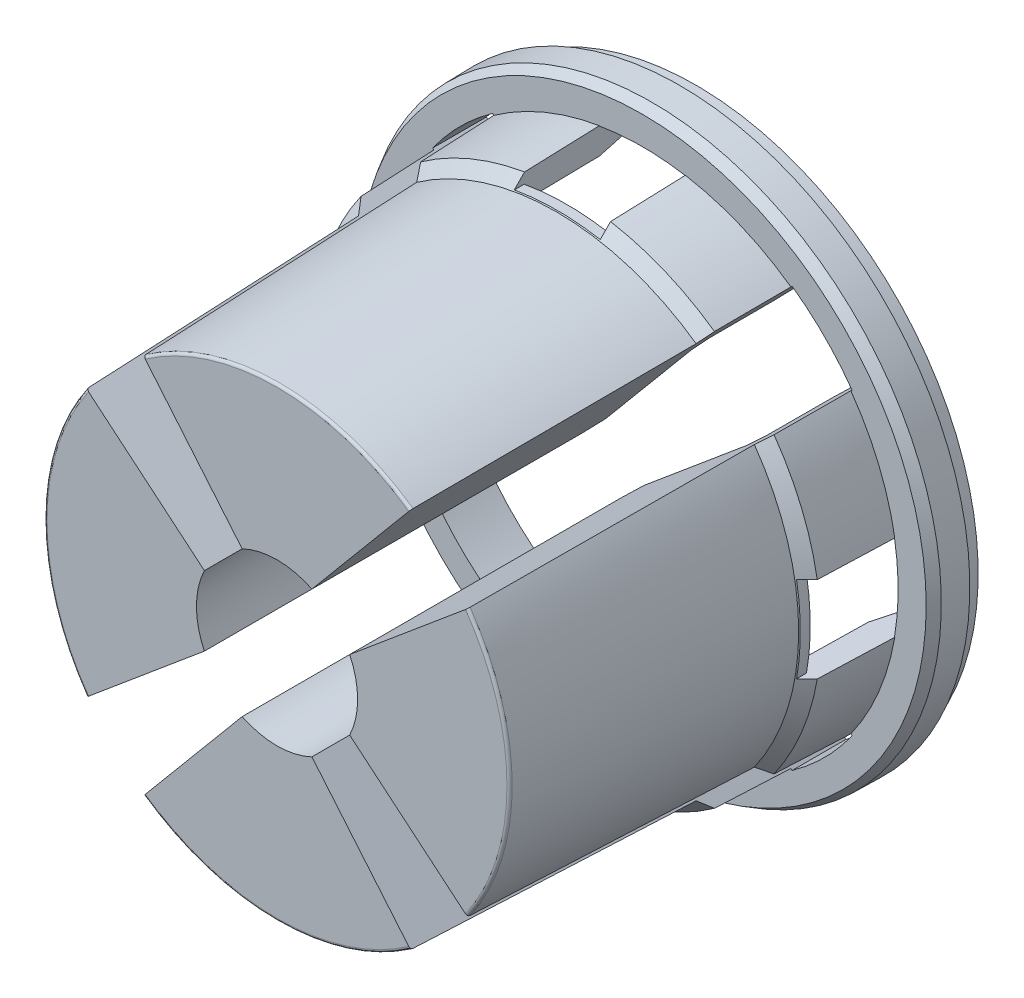
SolidWorks part; units mm, degrees
ref_plane "Plane1" through (0, 0, 0) normal (0, 0, 1) x (1, 0, 0)
ref_plane "Plane2" through (0, 0, 0) normal (0, 1, 0) x (1, 0, 0)
ref_plane "Plane3" through (0, 0, 0) normal (1, 0, 0) x (0, 0, -1)
sketch "Sketch1" plane through (0, 0, 0) normal (0, 0, 1) x (1, 0, 0)
  line L0 (0, 0) -> (0, 10) construction
  line L1 (0, 0) -> (0, -12.3667) construction
  circle A8 centre (0, 0) radius 5.4
  dimension "D4" = 10.8
extrude "Collar" add sketch "Sketch1" along normal blind 1 draft 1
sketch "Sketch2" plane through (0, 0, 0) normal (0, 0, 1) x (1, 0, 0)
  circle A0 centre (0, 0) radius 4.6
  dimension "D1" = 9.2
extrude "Sleeve outside" add sketch "Sketch2" along normal blind 7.8 draft 2
sketch "Sketch11" plane through (0, 0, 0) normal (0, 0, -1) x (-1, 0, 0)
  circle A0 centre (0, 0) radius 4.8
  dimension "D1" = 9.6
extrude "Extrude1" add sketch "Sketch11" against normal blind 2.6 draft 2
chamfer "Chamfer3" distance 0.2 angle 45 1 edges at (-4.7092, 0, 2.6) first distance on face at (-4.7092, 0, 2.6)
sketch "Sketch3" plane through (0, 0, 0) normal (0, 0, -1) x (-1, 0, 0)
  circle A0 centre (0, 0) radius 4.3
  dimension "D1" = 8.6
extrude "Entrence oversize hole for shaft" cut sketch "Sketch3" against normal blind 2.4 draft 1
chamfer "Chamfer4" distance 0.2 angle 45 1 edges at (-4.2581, 0, 2.4) first distance on face at (-4.2581, 0, 2.4)
chamfer "Chamfer1" distance 0.25 angle 75 1 edges at (-4.3, 0, 0) first distance on face at (-4.3, 0, 0)
sketch "Sketch6" plane through (0, 0, 7.8) normal (0, 0, 1) x (1, 0, 0)
  circle A0 centre (0, 0) radius 1.5
  dimension "D1" = 3
extrude "Shaft hole" cut sketch "Sketch6" against normal through all
chamfer "Chamfer to shaft hole" distance 0.1 angle 75 1 edges at (-1.5, 0, 2.4) first distance on face at (-1.5, 0, 2.4)
ref_axis "Axis2" through (0, 0, -0.3901) along (0, 0, 1)
sketch "Sketch4" plane through (0, 0, 1) normal (0, 0, 1) x (1, 0, 0)
  line L0 (-0.0325, 0.0325) -> (-10, 10) construction
  line L1 (-3.904, 2.7846) -> (-0.7263, 0.1253)
  line L2 (-0.1253, 0.7263) -> (-0.0325, 0.0325)
  line L3 (-0.0325, 0.0325) -> (-0.7263, 0.1253)
  line L5 (-0.1253, 0.7263) -> (-2.7846, 3.904)
  arc A0 (-2.7846, 3.904) -> (-3.904, 2.7846) centre (-0.0325, 0.0325) ccw
  point P6 (-0.0325, 0.0325)
  dimension "D1" = 4.75
  dimension "D2" = 0.7
extrude "Slots in sleeve(1)" cut sketch "Sketch4" along normal through all and the other way blind 10
pattern_circular "CirPattern2" count 4 over 360 about axis through (0, 0, -0.3901) along (0, 0, 1) of "Slots in sleeve(1)"
fillet "Fillet outside sleve end" radius 0.05 4 edges at (-4.3276, 0, 7.8) (0, -4.3276, 7.8) (4.3276, 0, 7.8) (0, 4.3276, 7.8)
sketch "Sketch7" plane through (0, 0, 0) normal (0, 0, -1) x (-1, 0, 0)
  line L0 (0, 0) -> (0, 10) construction
  line L3 (0, 4.2916) -> (0, -4.2916) construction
  line L4 (-0.8, 1.5326) -> (0.8, 1.5326)
  line L9 (0.8, 4.6923) -> (0.8, 1.5326)
  line L10 (-0.8, 4.6923) -> (-0.8, 1.5326)
  arc A0 (0.8, 4.6923) -> (-0.8, 4.6923) centre (0, 0) ccw
  point P14 (0, 1.5326)
  dimension "D1" = 1.6
extrude "small slot(1)" cut sketch "Sketch7" against normal up to surface (2.4 mm away) up to face at (0, 2.6049, 2.4)
ref_axis "Axis1" through (0, 0, -5.0403) along (0, 0, 1)
pattern_circular "CirPattern1" count 4 over 360 about axis through (0, 0, -5.0403) along (0, 0, 1) of "small slot(1)"
chamfer "Chamfer2" distance 0.1 angle 60 1 edges at (5.3825, 0, 1) first distance on face at (5.3825, 0, 1)
sketch "Sketch12" plane through (0, 0, 1) normal (0, 0, 1) x (1, 0, 0)
  line L0 (-0.8, 5.4598) -> (-0.8, 4.4537)
  line L1 (0.8, 4.4537) -> (0.8, 5.4598)
  line L2 (-0.8, 5.4598) -> (0.8, 5.4598)
  line L3 (-0.8, 4.6923) -> (-0.8, 1.5326) construction
  line L4 (0.8, 4.6923) -> (0.8, 1.5326) construction
  arc A0 (0.8, 4.4537) -> (-0.8, 4.4537) centre (0, 0) ccw
  dimension "D1" = 4.525
extrude "Cut-Extrude1" cut sketch "Sketch12" along normal blind 10
pattern_circular "CirPattern3" count 4 over 360 about axis through (0, 0, -5.0403) along (0, 0, 1) of "Cut-Extrude1"
sketch "Sketch14" plane through (0, 0, 0) normal (0, 0, -1) x (-1, 0, 0)
  circle A0 centre (0, 0) radius 5.25
extrude "Cut-Extrude2" cut sketch "Sketch14" against normal blind 0.3 flip side to cut
